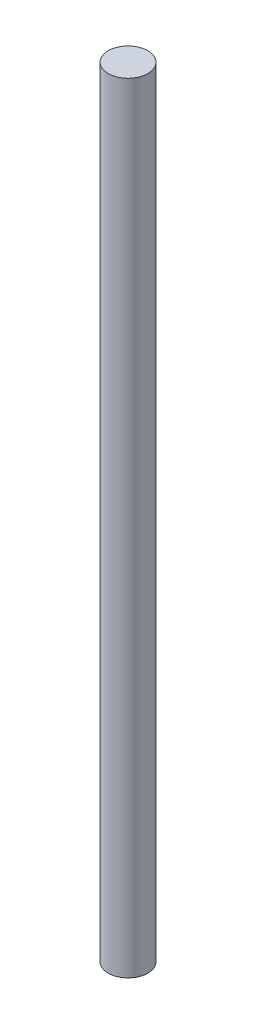
SolidWorks part; units mm, degrees
ref_plane "Front Plane" through (0, 0, 0) normal (0, 0, 1) x (1, 0, 0)
ref_plane "Top Plane" through (0, 0, 0) normal (0, 1, 0) x (1, 0, 0)
ref_plane "Right Plane" through (0, 0, 0) normal (1, 0, 0) x (0, 0, -1)
sketch "Sketch1" plane through (0, 0, 0) normal (0, 1, 0) x (1, 0, 0)
  circle A0 centre (0, 0) radius 1.935
  dimension "D1" = 3.87
extrude "Axle Body" add sketch "Sketch1" along normal blind 76.2
equation "\"CageLeftBottomEdge\"=22.11mm"
equation "\"CageLeftTopEdge\"=22.11mm"
equation "\"CageRightBottomEdge\"=21.63mm"
equation "\"CageRightTopEdge\"=21.63mm"
equation "\"CageHeight\"=86.04mm"
equation "\"CageLength\"=73.76mm"
equation "\"CageTopScrewClearance\"=10mm"
equation "\"CageBottomScrewClearance\"=25mm"
equation "\"CageLeftTopDepth\"= 11.65mm"
equation "\"CageLeftBottomDepth\"=11.11mm"
equation "\"CageLeftTopHeight\"=8.56175mm"
equation "\"CageLeftBottomHeight\"=16mm"
equation "\"CageRightTopDepth\"= 11.05mm"
equation "\"CageRightBottomDepth\"=10.58mm"
equation "\"CageRightTopHeight\"=9.6mm"
equation "\"CageRightBottomHeight\"=15.49mm"
equation "\"CageLeftTopChannelDepth\"=2.41908mm"
equation "\"CageLeftBottomChannelDepth\"=2.588mm"
equation "\"CageLeftChannelHeight\"=11.7mm"
equation "\"CageRightTopChannelDepth\"=2.32mm"
equation "\"CageRightBottomChannelDepth\"=2.318mm"
equation "\"CageRightChannelHeight\"=10mm"
equation "\"CageChanRelHeight\"=23.99mm"
equation "\"CageChanRelDepth\"=5.492mm"
equation "\"CageChamberRadius\"=16.261mm"
equation "\"CageScrewDiameter\"=4.8mm"
equation "\"CageSetScrewDiameter\"=3.5mm"
equation "\"CageAxleRadius\"=6.639mm"
equation "\"CageAxleKeyHeight\"=1.619mm"
equation "\"CageAxleKeyWidth\"=2.662mm"
equation "\"CageHoseWindowWidth\"=16.29mm"
equation "\"CageHoseWindowHeight\"=26.5mm"
equation "\"CageHoseWindow-Edge\"=8.89mm"
equation "\"CageScrew-VerticalEdge\"=5.0mm"
equation "\"CageScrew-HorizontalEdge\"=7.5mm"
equation "\"CageScrew-HoseCornerScrewEdge\"=4.45mm"
equation "\"CageAxle-BottomEdge\"=56.05mm"
equation "\"CageAxle-FrontEdge\"=46.03mm"
equation "\"CageBackSetScrew-Axle\"=40mm"
equation "\"CageFrontSetScrew-Axle\"=22mm"
equation "\"CageVelocityWindow-BackEdge\"=34.8mm"
equation "\"CageVelocityWindow-BottomEdge\"=27.55mm"
equation "\"CageVelocityWindowHeight\"=22.29mm"
equation "\"CageVelocityWindowWidth\"=12.61mm"
equation "\"TriggerSlot-BottomEdge\"=6.35mm"
equation "\"TriggerSlot-FrontEdge\"=15mm"
equation "\"TriggerSlotSize\"=6.7mm"
equation "\"TriggerRackOffset\"=.236224in"
equation "\"TriggerSlotSizeInt\"=.25in"
equation "\"MotorMountLegLength\"=.25in"
equation "\"GearOffset\"=.264907in"
equation "\"TriggerSlotSpacing\"=.25in"
equation "\"TriggerMiniSlotWidth\"=3.5mm"
equation "\"TriggerRackWidth\"=6.5mm"
equation "\"whitemotordepth\"=11.27mm"
equation "\"whitemotorbackdepth\"=3.845mm"
equation "\"whitemotoraxledepth\" = 3.5mm"
equation "\"whitemotoraxleoffset\"=11.4mm"
equation "\"whitemotorwidth\"=12.07mm"
equation "\"whitemotorheight\"=16.68mm"
equation "\"whitemotorcylinderlength\" =13.04mm"
equation "\"whitemotorcylinderradius\"=3.845mm"
equation "\"whitemotorcylinderoffset\"=2.35mm"
equation "\"whitemotorcutoutlength\"=1.88mm"
equation "\"whitemotorouterrad\"=5mm"
equation "\"whitemotorinnerrad\"=2.95mm"
equation "\"elasticracklength\"=2in"
equation "\"elasticrackpegsize\"=.25in"
equation "\"elasticrackpegbuffer\"=.125in"
equation "\"elasticrackpegspacing\"=1.76476378in"
equation "\"elasticbaybuffer\"=.25in"
equation "\"elasticdepth\"=.125in"
equation "\"elasticbaydepth\"=.75in"
equation "\"motormountwidth\"=12mm"
equation "\"motormountcornerfillet\"=3mm"
equation "\"pandiscradius\"=14in"
equation "\"towermaterialwidth\"=.25in"
equation "\"towerslotlength\"=.5in"
equation "\"towermarkerspace\"=5in"
equation "\"towerslothorizoffset\"=1in"
equation "\"towerslothorizspacing\"=2in"
equation "\"towerslotvertoffset\"=3in"
equation "\"towerslotvertspacing\"=1in"
equation "\"towerheight\"=12in"
equation "\"towerupslot\"=1in"
equation "\"toweraxle\"=.5in"
equation "\"stepperouterrad\"=10mm"
equation "\"stepperscrewsize\"=3.45mm"
equation "\"stepperscrewc2c\"=49.5mm"
equation "\"stepperdepthoffset\"=24mm"
equation "\"stepperhorizoffset\"=22.91mm"
equation "\"shaftslotOD\"=18.8mm"
equation "\"shaftslotID\"=13.28mm"
equation "\"shaftkeywidth\"=2.67mm"
equation "\"shaftkeydepth\"=1.8mm"
equation "\"shaftcollartotaldepth\"=12.5mm"
equation "\"shaftsquaredepth\"=6mm"
equation "\"shaftsetscrewsize\"=3.5mm"
equation "\"shaftkeytightdepth\"=1.85mm"
equation "\"shaftslottightID\"=12.78mm"
equation "\"shaftsetscrewoffset\"=9mm"
equation "\"cagecollartotaldepth\"=10mm"
equation "\"cagecollartotalwidth\"=35mm"
equation "\"cagecollarbasedepth\"=4mm"
equation "\"ajaxaxlesize\"=3.87mm"
equation "\"ajax4020gap\"=29.5mm"
equation "\"ajax4010gap\"=24.5mm"
equation "\"D1@Sketch1\"=\"ajaxaxlesize\""
equation "\"D1@Axle Body\"=\"towerslotvertspacing\"+\"towerslotlength\"+(6*\"towermaterialwidth\")"
equation "\"gearhubintdiam\"=30mm"
equation "\"gearhubintwid\"=15mm"
equation "\"towerspeedwidth\"=2in"
equation "\"towerspeedheight\"=8in"
equation "\"towerspeedgap\"=2in"
equation "\"stepperaxleflat\"=.037in"
equation "\"stepperaxlerad\"=0.11811024in"
equation "\"ajaxinnercut\"=2.3mm"
equation "\"ajaxwidth\"=6.1mm"
equation "\"ajaxdiametral\"=25.8854"
equation "\"ajaxcutoutdepth\"=2.3mm"
equation "\"ajax20hubbuffer\"=6.1mm"
equation "\"ajax20hubholeoffset\"=.19685in"
equation "\"ajax20hubholesize\"=.059055in"
equation "\"ajax20cutoutint\"=13.4mm"
equation "\"ajax40hubholesize\"=7.21mm"
equation "\"ajax40hubholeoffset\"=10mm"
equation "\"ajax40hubbuffer\"=8.9mm"
equation "\"ajax40cutoutint\"=32.6mm"
equation "\"bearingpandiscrad\"=6.8in"
equation "\"bearingpandiscang\"=48.75deg"
equation "\"bearingclearholedist\"=4.7345in"
equation "\"bearingclearholesize\"=.5in"
equation "\"bearingclearholeang\"=22.5deg"
equation "\"bearingmountholedist\"=4.25in"
equation "\"bearingwirehole\"=1.5in"
equation "\"no6diam\"=.146in"
equation "\"shortconangle\"=20deg"
equation "\"shortconlen\"=.875in"
equation "\"longconlen\"=1.25in"
equation "\"longconangle\"=15deg"
